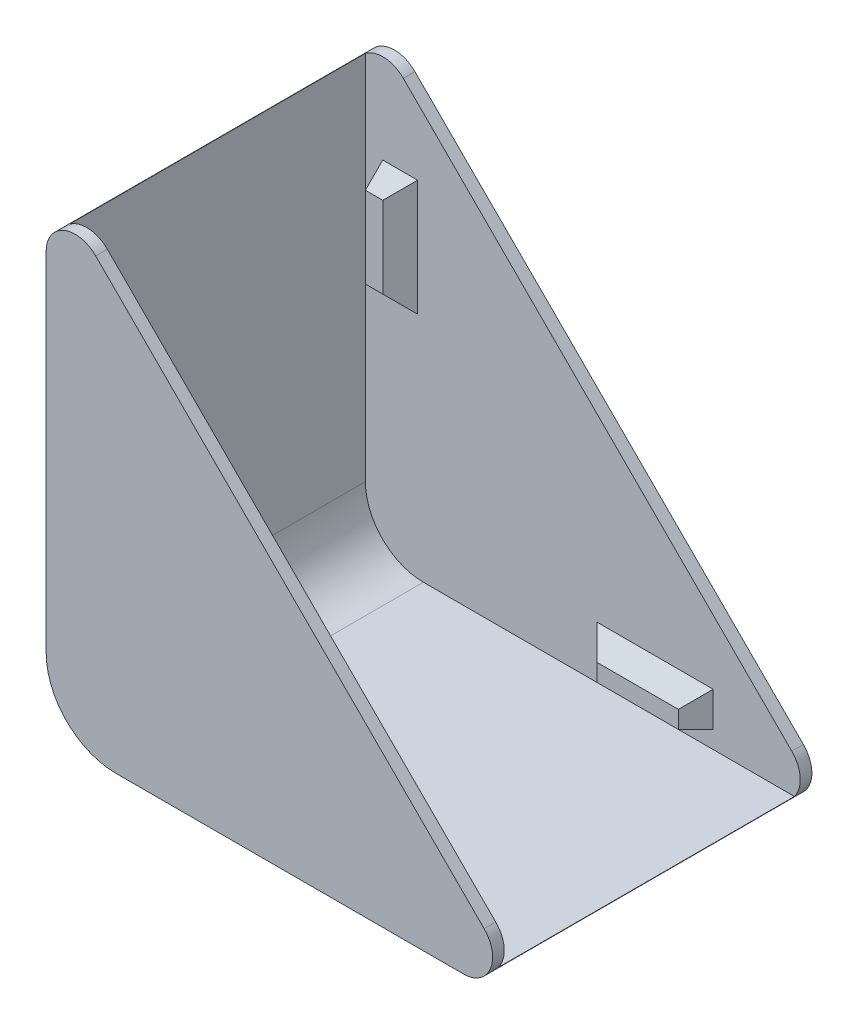
SolidWorks part; units mm, degrees
ref_plane "Plan de face" through (0, 0, 0) normal (0, 0, 1) x (1, 0, 0)
ref_plane "Plan de dessus" through (0, 0, 0) normal (0, 1, 0) x (1, 0, 0)
ref_plane "Plan de droite" through (0, 0, 0) normal (1, 0, 0) x (0, 0, -1)
sketch "Esquisse1" plane through (0, 0, 0) normal (0, 0, 1) x (1, 0, 0)
  line L0 (0, 0) -> (0, 80)
  line L1 (0, 80) -> (80, 0)
  line L2 (80, 0) -> (0, 0)
  dimension "D1" = 80
  dimension "D2" = 80
extrude "Boss.-Extru.1" add sketch "Esquisse1" along normal mid plane 51
sketch "Esquisse4" plane through (0, 0, 0) normal (1, 0, 0) x (0, 0, -1)
  line L0 (-61.9556, 0) -> (61.9556, 0) construction
  point P4 (0, 0)
fillet "Congé1" radius 10 1 edges at (0, 0, 0)
shell "Coque1" thickness 2 removed face at (40, 40, 0) outward yes
fillet "Congé2" radius 5 2 edges at (82, -2, 0) (-2, 82, 0)
sketch "Esquisse2" plane through (0, 0, 25.5) normal (0, 0, -1) x (-1, 0, 0)
  line L0 (-59.9289, 3) -> (-59.9289, 9)
  line L1 (-59.9289, 3) -> (-39.9289, 3)
  line L2 (-59.9289, 9) -> (-39.9289, 9)
  line L3 (-39.9289, 3) -> (-39.9289, 9)
  line L4 (-10, 0) -> (-73.9289, 0) construction
  line L5 (-3, 39.4964) -> (-3, 59.4964)
  line L6 (-3, 39.4964) -> (-9, 39.4964)
  line L7 (-3, 59.4964) -> (-9, 59.4964)
  line L8 (-9, 39.4964) -> (-9, 59.4964)
  line L9 (0, 73.9289) -> (0, 10) construction
  arc A0 (-73.4645, 6.5355) -> (-73.9289, 0) centre (-69.9289, 3) ccw construction
  dimension "D1" = 3
  dimension "D2" = 20
  dimension "D3" = 6
  dimension "D4" = 10
  dimension "D5" = 20
  dimension "D6" = 3
  dimension "D7" = 6
extrude "Boss.-Extru.2" add sketch "Esquisse2" along normal blind 3
chamfer "Chanfrein1" distance 3 6 edges at (49.9289, 9, 22.5) (59.9289, 6, 22.5) (39.9289, 6, 22.5) (6, 39.4964, 22.5) (6, 59.4964, 22.5) (9, 49.4964, 22.5)
mirror "Symétrie1" about plane through (0, 0, 0) normal (0, 0, 1) of "Chanfrein1", "Boss.-Extru.2"
equation "\"longueur\"=80"
equation "\"D1@Esquisse1\"=\"longueur\""
equation "\"D2@Esquisse1\"=\"longueur\""
equation "\"largeur_ext\"=10"
equation "\"D1@Boss.-Extru.1\"=\"largeur_int\""
equation "\"largeur_int\"= 51"
equation "\"conges\"=10"
equation "\"D1@Congé1\"=\"conges\""
